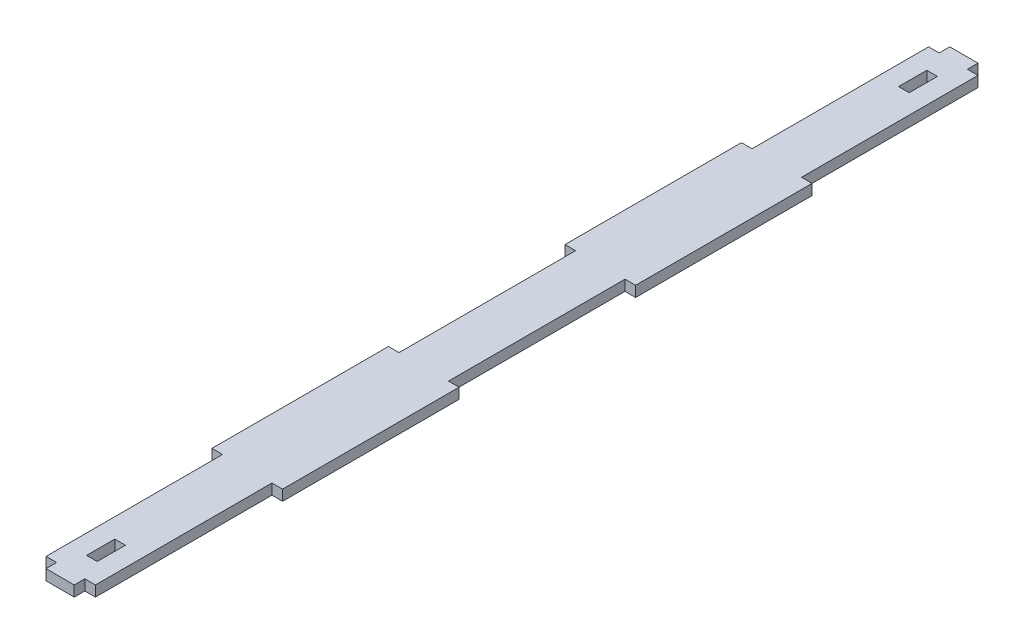
SolidWorks part; units mm, degrees
ref_plane "Alzado" through (0, 0, 0) normal (0, 0, 1) x (1, 0, 0)
ref_plane "Planta" through (0, 0, 0) normal (0, 1, 0) x (1, 0, 0)
ref_plane "Vista lateral" through (0, 0, 0) normal (1, 0, 0) x (0, 0, -1)
sketch "Croquis1" plane through (0, 0, 0) normal (0, 1, 0) x (1, 0, 0)
  line L0 (10, 253.1162) -> (14, 253.1162)
  line L1 (20, 50.1162) -> (20, 100.1162)
  line L2 (3, 200.1162) -> (0, 200.1162)
  line L3 (17, 250.1162) -> (17, 200.1162)
  line L4 (3, 100.1162) -> (3, 150.1162)
  line L5 (20, 150.1162) -> (17, 150.1162)
  line L6 (20, 150.1162) -> (20, 200.1162)
  line L7 (17, 200.1162) -> (20, 200.1162)
  line L8 (0, 200.1162) -> (0, 150.1162)
  line L9 (0, 100.1162) -> (0, 50.1162)
  line L10 (17, 250.1162) -> (14, 250.1162)
  line L11 (3, 125.1162) -> (17, 125.1162) construction
  line L12 (17, 150.1162) -> (17, 100.1162)
  line L13 (3, 150.1162) -> (3, 100.1162)
  line L14 (17, 50.1162) -> (20, 50.1162)
  line L15 (10, 253.1162) -> (10, 240.1162) construction
  line L16 (20, 100.1162) -> (17, 100.1162)
  line L17 (3, 100.1162) -> (0, 100.1162)
  line L18 (17, 50.1162) -> (17, 0.1162)
  line L19 (0, 150.1162) -> (3, 150.1162)
  line L20 (0, 100.1162) -> (3, 100.1162)
  line L21 (10, -2.8838) -> (10, 10.1162) construction
  line L22 (10, 253.1162) -> (6, 253.1162)
  line L23 (3, 50.1162) -> (0, 50.1162)
  line L24 (6, 253.1162) -> (6, 250.1162)
  line L25 (11.5, 6.1162) -> (10, 6.1162)
  line L26 (11.5, 14.1162) -> (11.5, 6.1162)
  line L27 (14, 253.1162) -> (14, 250.1162)
  line L28 (0, 100.1162) -> (0, 50.1162)
  line L29 (8.5, 14.1162) -> (11.5, 14.1162)
  line L30 (6, 250.1162) -> (3, 250.1162)
  line L31 (17, 0.1162) -> (14, 0.1162)
  line L32 (8.5, 6.1162) -> (8.5, 14.1162)
  line L33 (14, -2.8838) -> (6, -2.8838)
  line L34 (6, -2.8838) -> (6, 0.1162)
  line L35 (14, -2.8838) -> (14, 0.1162)
  line L36 (6, 0.1162) -> (3, 0.1162)
  line L37 (10, 6.1162) -> (8.5, 6.1162)
  line L38 (10, 10.1162) -> (10, 6.1162)
  line L43 (3, 0.1162) -> (3, 50.1162)
  line L44 (3, 200.1162) -> (3, 250.1162)
  line L45 (10, 240.1162) -> (10, 244.1162)
  line L46 (10, 244.1162) -> (8.5, 244.1162)
  line L47 (8.5, 244.1162) -> (8.5, 236.1162)
  line L48 (8.5, 236.1162) -> (11.5, 236.1162)
  line L49 (11.5, 236.1162) -> (11.5, 244.1162)
  line L50 (11.5, 244.1162) -> (10, 244.1162)
  dimension "D2" = 50
  dimension "D3" = 50
  dimension "D4" = 13
  dimension "D5" = 3
  dimension "D6" = 50
  dimension "D7" = 50
  dimension "D8" = 3
  dimension "D9" = 4
  dimension "D10" = 1.5
  dimension "D11" = 8
  dimension "D12" = 3
  dimension "D13" = 50
  dimension "D14" = 50
  dimension "D15" = 50
  dimension "D16" = 50
  dimension "D17" = 50
  dimension "D18" = 50
extrude "Saliente-Extruir1" add sketch "Croquis1" along normal blind 3 contours L44 L2 L8 L19 L4 L17 L9 L23 L43 L36 L34 L33 L35 L31 L18 L14 L1 L16 L12 L5 L6 L7 L10 L27 L0 L50 L49 L48 L47 L46 L22 L24 L30 region at (10, 0, -125.1162)
